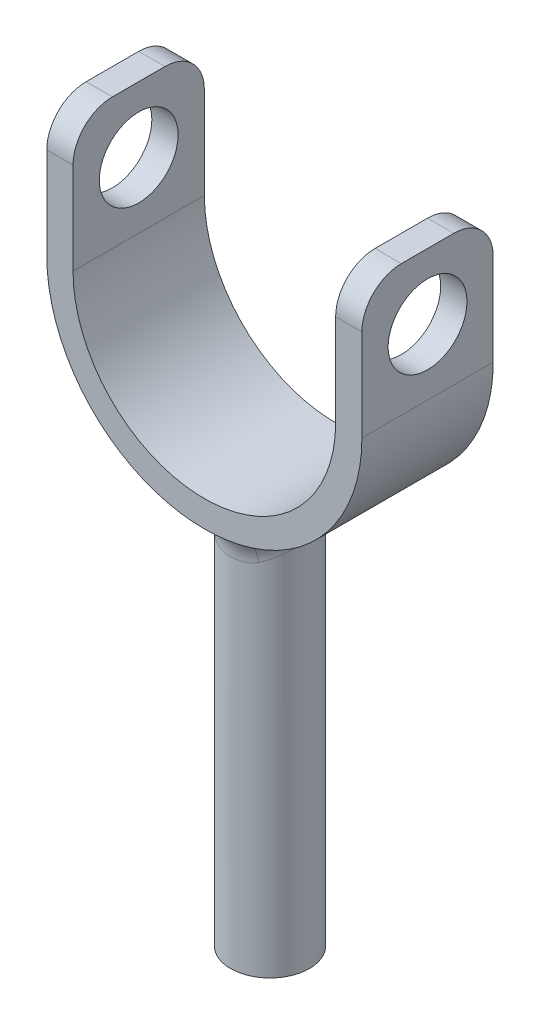
SolidWorks part; units mm, degrees
ref_plane "Alzado" through (0, 0, 0) normal (0, 0, 1) x (1, 0, 0)
ref_plane "Planta" through (0, 0, 0) normal (0, 1, 0) x (1, 0, 0)
ref_plane "Vista lateral" through (0, 0, 0) normal (1, 0, 0) x (0, 0, -1)
sketch "Croquis1" plane through (0, 0, 0) normal (0, 0, 1) x (1, 0, 0)
  line L0 (-60, 0) -> (-60, 50)
  line L1 (-60, 50) -> (-50, 50)
  line L2 (-50, 50) -> (-50, 0)
  line L3 (50, 0) -> (50, 50)
  line L4 (50, 50) -> (60, 50)
  line L5 (60, 50) -> (60, 0)
  arc A0 (-60, 0) -> (60, 0) centre (0, 0) ccw
  arc A1 (-50, 0) -> (50, 0) centre (0, 0) ccw
  dimension "D1" = 60
  dimension "D2" = 50
  dimension "D3" = 50
extrude "Saliente-Extruir1" add sketch "Croquis1" against normal blind 50
fillet "Redondeo1" radius 15 1 edges at (-55, 50, 0)
fillet "Redondeo2" radius 15 1 edges at (55, 50, 0)
fillet "Redondeo3" radius 15 2 edges at (-55, 50, -50) (55, 50, -50)
sketch "Croquis2" plane through (60, 0, 0) normal (1, 0, 0) x (0, 0, -1)
  line L0 (25, 50) -> (25, 25) construction
  line L1 (35, 50) -> (15, 50) construction
  circle A0 centre (25, 25) radius 15
  dimension "D2" = 30
  dimension "D1" = 25
extrude "Cortar-Extruir1" cut sketch "Croquis2" against normal through all
ref_plane "Plano2" through (0, -70, 0) normal (0, 1, 0) x (1, 0, 0)
sketch "Croquis6" plane through (0, -70, 0) normal (0, 1, 0) x (1, 0, 0)
  line L0 (0, 50) -> (0, 0) construction
  line L1 (50, 50) -> (-50, 50) construction
  circle A0 centre (0, 25) radius 15
  dimension "D1" = 30
extrude "Saliente-Extruir5" add sketch "Croquis6" against normal blind 140 and the other way up to next
fillet "Redondeo4" radius 15 1 edges at (-2.9337, -59.9282, -10.2897)
